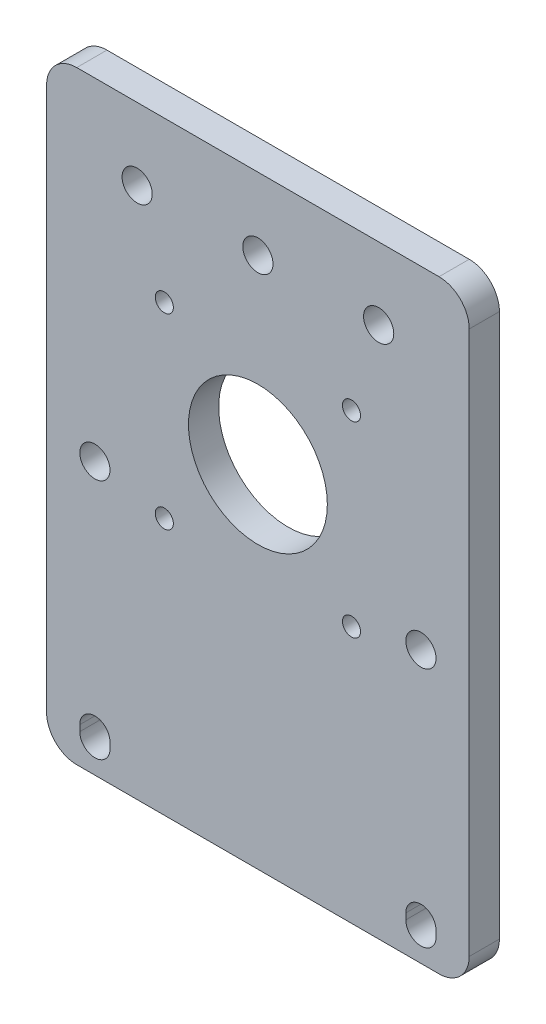
SolidWorks part; units mm, degrees
ref_plane "Front" through (0, 0, 0) normal (0, 0, 1) x (1, 0, 0)
ref_plane "Top" through (0, 0, 0) normal (0, 1, 0) x (1, 0, 0)
ref_plane "Right" through (0, 0, 0) normal (1, 0, 0) x (0, 0, -1)
sketch "Sketch4" plane through (0, 0, 0) normal (0, 0, 1) x (1, 0, 0)
  line L0 (-27, -44) -> (-27, -45) construction
  line L1 (-35, 50) -> (35, 50)
  line L2 (-35, 50) -> (-35, -50)
  line L3 (-35, -50) -> (35, -50)
  line L4 (35, 50) -> (35, -50)
  line L5 (-35, 50) -> (35, -50) construction
  line L6 (-35, -50) -> (35, 50) construction
  line L7 (-24.5, -44) -> (-24.5, -45)
  line L8 (-29.5, -44) -> (-29.5, -45)
  line L9 (0, -47.1607) -> (0, 39.6245) construction
  line L10 (27, -44) -> (27, -45) construction
  line L11 (24.5, -44) -> (24.5, -45)
  line L12 (29.5, -44) -> (29.5, -45)
  circle A0 centre (-27, -5) radius 2.5
  arc A1 (-24.5, -44) -> (-29.5, -44) centre (-27, -44) ccw
  arc A2 (-29.5, -45) -> (-24.5, -45) centre (-27, -45) ccw
  arc A3 (24.5, -44) -> (29.5, -44) centre (27, -44) cw
  arc A4 (29.5, -45) -> (24.5, -45) centre (27, -45) cw
  circle A5 centre (27, -5) radius 2.5
  point P0 (0, 0)
  point P10 (-27, -44.5)
  point P19 (27, -44.5)
  dimension "D3" = 27
  dimension "D6" = 2.5
  dimension "D8" = 5
  dimension "D1" = 70
  dimension "D2" = 100
  dimension "D4" = 39
  dimension "D5" = 1
  dimension "D7" = 5
extrude "Boss-Extrude2" add sketch "Sketch4" along normal blind 5
sketch "Sketch5" plane through (0, 0, 5) normal (0, 0, 1) x (1, 0, 0)
  line L0 (0, 46.583) -> (0, -17.262) construction
  line L1 (-44.8343, 8.0767) -> (52.8956, 8.0767) construction
  circle A0 centre (0, 8.0767) radius 11.5
  circle A1 centre (27, -5) radius 2.5 construction
  circle A2 centre (-15.5, 23.5767) radius 1.5
  circle A9 centre (15.5, 23.5767) radius 1.5
  circle A10 centre (15.5, -7.4233) radius 1.5
  circle A11 centre (-15.5, -7.4233) radius 1.5
  dimension "D1" = 23
  dimension "D3" = 3
  dimension "D2" = 30
  dimension "D4" = 15.5
  dimension "D5" = 15.5
extrude "Cut-Extrude2" cut sketch "Sketch5" against normal through all
sketch "Sketch6" plane through (0, 0, 5) normal (0, 0, 1) x (1, 0, 0)
  line L0 (0, 37.2831) -> (0, 4.0651) construction
  line L1 (-10, 48.0767) -> (10, 48.0767) construction
  line L2 (-10, 48.0767) -> (-10, 28.0767) construction
  line L3 (-10, 28.0767) -> (10, 28.0767) construction
  line L4 (10, 48.0767) -> (10, 28.0767) construction
  line L5 (-10, 48.0767) -> (10, 28.0767) construction
  line L6 (-10, 28.0767) -> (10, 48.0767) construction
  circle A0 centre (0, 8.0767) radius 11.5 construction
  circle A1 centre (20, 38.0767) radius 2.5
  circle A2 centre (-20, 38.0767) radius 2.5
  circle A3 centre (0, 38.0767) radius 2.5
  point P0 (0, 38.0767)
  dimension "D4" = 5
  dimension "D6" = 5
  dimension "D1" = 20
  dimension "D2" = 20
  dimension "D3" = 30
  dimension "D5" = 20
extrude "Cut-Extrude3" cut sketch "Sketch6" against normal through all
fillet "Fillet1" radius 5 4 edges at (-35, -50, 2.5) (35, -50, 2.5) (35, 50, 2.5) (-35, 50, 2.5)
